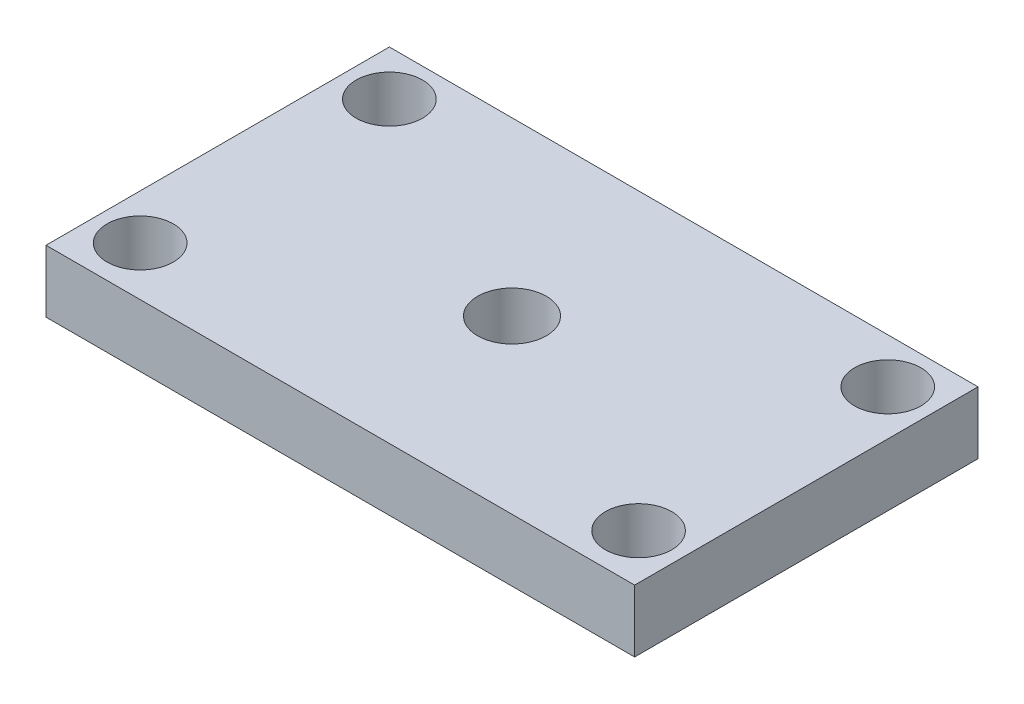
SolidWorks part; units mm, degrees
ref_plane "Front Plane" through (0, 0, 0) normal (0, 0, 1) x (1, 0, 0)
ref_plane "Top Plane" through (0, 0, 0) normal (0, 1, 0) x (1, 0, 0)
ref_plane "Right Plane" through (0, 0, 0) normal (1, 0, 0) x (0, 0, -1)
sketch "Sketch1" plane through (0, 0, 0) normal (0, 1, 0) x (1, 0, 0)
  line L0 (4.6, 30.4) -> (0, 30.4) construction
  line L1 (0, 0) -> (60, 0)
  line L2 (0, 0) -> (0, 35)
  line L3 (0, 35) -> (60, 35)
  line L4 (60, 0) -> (60, 35)
  line L5 (4.6, 30.4) -> (55.4, 30.4) construction
  line L6 (4.6, 30.4) -> (4.6, 5) construction
  line L7 (4.6, 5) -> (55.4, 5) construction
  line L8 (55.4, 30.4) -> (55.4, 5) construction
  line L9 (4.6, 30.4) -> (4.6, 35) construction
  circle A0 centre (4.6, 30.4) radius 3.3782
  circle A1 centre (55.4, 30.4) radius 3.3782
  circle A2 centre (4.6, 5) radius 3.3782
  circle A3 centre (55.4, 5) radius 3.3782
  circle A4 centre (30, 17.5) radius 3.5
  point P13 (30, 30.4)
  point P14 (30, 35)
  point P20 (60, 17.5)
  dimension "D5" = 6.7564
  dimension "D6" = 7
  dimension "D1" = 60
  dimension "D2" = 35
  dimension "D3" = 50.8
  dimension "D4" = 25.4
extrude "Boss-Extrude1" add sketch "Sketch1" along normal blind 6.35
